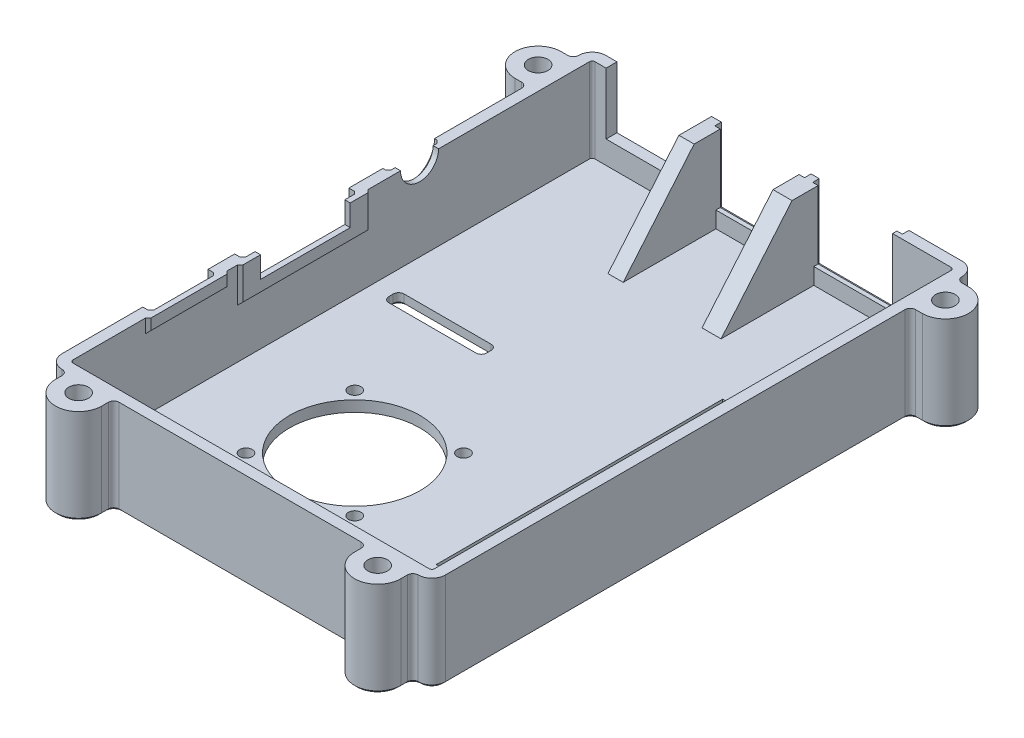
SolidWorks part; units mm, degrees
ref_plane "Front Plane" through (0, 0, 0) normal (0, 0, 1) x (1, 0, 0)
ref_plane "Top Plane" through (0, 0, 0) normal (0, 1, 0) x (1, 0, 0)
ref_plane "Right Plane" through (0, 0, 0) normal (1, 0, 0) x (0, 0, -1)
sketch "Sketch2" plane through (0, 0, 0) normal (0, 1, 0) x (1, 0, 0)
  line L1 (2.5, 0) -> (68, 0)
  line L2 (0, 2.5) -> (0, 97.5)
  line L3 (2.5, 100) -> (68, 100)
  line L4 (70.5, 2.5) -> (70.5, 97.5)
  arc A0 (0, 2.5) -> (2.5, 0) centre (2.5, 2.5) ccw
  arc A1 (68, 0) -> (70.5, 2.5) centre (68, 2.5) ccw
  arc A2 (70.5, 97.5) -> (68, 100) centre (68, 97.5) ccw
  arc A3 (2.5, 100) -> (0, 97.5) centre (2.5, 97.5) ccw
  point P7 (0, 0)
  point P10 (70.5, 0)
  point P13 (70.5, 100)
  point P16 (0, 100)
  dimension "D3" = 2.5
  dimension "D1" = 70.5
  dimension "D2" = 100
extrude "Base" add sketch "Sketch2" along normal blind 17.5
shell "Shell" thickness 2 removed face at (35.25, 17.5, -50)
sketch "Sketch14" plane through (0, 0, 0) normal (0, -1, 0) x (1, 0, 0)
  line L0 (35.25, 0) -> (35.25, -100) construction
  line L2 (68, -100) -> (2.5, -100) construction
  line L3 (-2.2, -88) -> (0, -88)
  line L4 (0, -97.5) -> (0, -2.5) construction
  line L5 (0, -88) -> (0, -96.5)
  line L6 (0, -96.5) -> (-2.2, -96.5)
  line L7 (3.5, 2.2) -> (3.5, 0)
  line L8 (2.5, 0) -> (68, 0) construction
  line L9 (3.5, 0) -> (12, 0)
  line L10 (12, 0) -> (12, 2.2)
  line L11 (72.7, -88) -> (70.5, -88)
  line L12 (70.5, -96.5) -> (72.7, -96.5)
  line L13 (70.5, -88) -> (70.5, -96.5)
  line L14 (58.5, 0) -> (58.5, 2.2)
  line L15 (67, 0) -> (58.5, 0)
  line L16 (67, 2.2) -> (67, 0)
  line L17 (2.5, 0) -> (68, 0) construction
  arc A0 (-2.2, -88) -> (-2.2, -96.5) centre (-2.2, -92.25) ccw
  arc A1 (3.5, 2.2) -> (12, 2.2) centre (7.75, 2.2) cw
  arc A2 (72.7, -88) -> (72.7, -96.5) centre (72.7, -92.25) cw
  arc A3 (67, 2.2) -> (58.5, 2.2) centre (62.75, 2.2) ccw
  dimension "D1" = 2.2
  dimension "D2" = 8.5
  dimension "D3" = 3.5
  dimension "D4" = 3.5
extrude "Clamps" add sketch "Sketch14" against normal up to surface (17.5 mm away) up to face at (35.25, 17.5, -50)
fillet "Clamp Fillets" radius 1 8 edges at (58.5, 8.75, 0) (67, 8.75, 0) (12, 8.75, 0) (3.5, 8.75, 0) (0, 8.75, -96.5) (0, 8.75, -88) (70.5, 8.75, -88) (70.5, 8.75, -96.5)
sketch "Sketch20" plane through (0, 0, 0) normal (0, -1, 0) x (1, 0, 0)
  circle A0 centre (7.75, 2.2) radius 1.8
  circle A1 centre (62.75, 2.2) radius 1.8
  circle A2 centre (72.7, -92.25) radius 1.8
  circle A3 centre (-2.2, -92.25) radius 1.8
  arc A4 (12, 2.2) -> (3.5, 2.2) centre (7.75, 2.2) ccw construction
  arc A5 (67, 2.2) -> (58.5, 2.2) centre (62.75, 2.2) ccw construction
  arc A6 (-2.2, -88) -> (-2.2, -96.5) centre (-2.2, -92.25) ccw construction
  arc A7 (72.7, -96.5) -> (72.7, -88) centre (72.7, -92.25) ccw construction
  dimension "D1" = 3.6
extrude "Clamp Holes" cut sketch "Sketch20" against normal through all
sketch "Sketch21" plane through (0, 0, 0) normal (0, -1, 0) x (1, 0, 0)
  circle A0 centre (7.75, 2.2) radius 2.9
  circle A1 centre (62.75, 2.2) radius 2.9
  circle A2 centre (72.7, -92.25) radius 2.9
  circle A3 centre (-2.2, -92.25) radius 2.9
  circle A4 centre (-2.2, -92.25) radius 1.8 construction
  circle A5 centre (7.75, 2.2) radius 1.8 construction
  circle A6 centre (62.75, 2.2) radius 1.8 construction
  circle A7 centre (72.7, -92.25) radius 1.8 construction
  dimension "D1" = 5.8
extrude "Clamp Countersinks" cut sketch "Sketch21" against normal blind 3.4
chamfer "Clamp Countersink Chamfers" distance 0.3 angle 45 4 edges at (-2.2, 0, -95.15) (72.7, 0, -95.15) (62.75, 0, -0.7) (7.75, 0, -0.7)
sketch "Sketch24" plane through (0, 0, -100) normal (0, 0, -1) x (-1, 0, 0)
  line L0 (-68, 17.5) -> (-2.5, 17.5) construction
  line L1 (-57.25, 17.5) -> (-42.75, 17.5)
  line L2 (-57.25, 17.5) -> (-57.25, 5)
  line L3 (-57.25, 5) -> (-42.75, 5)
  line L4 (-42.75, 17.5) -> (-42.75, 5)
  line L6 (0, 17.5) -> (0, 0) construction
  line L7 (-39.25, 17.5) -> (-24.75, 17.5)
  line L8 (-39.25, 17.5) -> (-39.25, 5)
  line L9 (-39.25, 5) -> (-24.75, 5)
  line L10 (-24.75, 17.5) -> (-24.75, 5)
  dimension "D1" = 14.5
  dimension "D2" = 24.75
  dimension "D3" = 42.75
  dimension "D4" = 12.5
extrude "USB Cutout" cut sketch "Sketch24" against normal blind 18.25
sketch "Sketch25" plane through (0, 0, -100) normal (0, 0, -1) x (-1, 0, 0)
  line L0 (-42.75, 17.5) -> (-39.25, 17.5) construction
  line L1 (-41.75, 17.5) -> (-58.25, 17.5)
  line L2 (-41.75, 17.5) -> (-41.75, 4)
  line L3 (-41.75, 4) -> (-58.25, 4)
  line L4 (-58.25, 17.5) -> (-58.25, 4)
  line L6 (-24.75, 17.5) -> (-2.5, 17.5) construction
  line L7 (-23.75, 17.5) -> (-40.25, 17.5)
  line L8 (-23.75, 17.5) -> (-23.75, 4)
  line L9 (-23.75, 4) -> (-40.25, 4)
  line L10 (-40.25, 17.5) -> (-40.25, 4)
  line L12 (-57.25, 17.5) -> (-57.25, 5) construction
  line L13 (-42.75, 5) -> (-42.75, 17.5) construction
  line L14 (-39.25, 17.5) -> (-39.25, 5) construction
  line L15 (-24.75, 5) -> (-24.75, 17.5) construction
  point P18 (-57.25, 11.25)
  dimension "D1" = 1
  dimension "D2" = 1
  dimension "D3" = 1
  dimension "D4" = 1
  dimension "D5" = 13.5
extrude "USB Approach" cut sketch "Sketch25" against normal blind 1.2
sketch "Sketch26" plane through (42.75, 0, 0) normal (1, 0, 0) x (0, 0, -1)
  line L0 (98, 2) -> (98, 17.5)
  line L1 (98, 17.5) -> (94, 17.5)
  line L2 (98, 2) -> (80.95, 2)
  line L3 (80.95, 2) -> (94, 17.5)
  line L4 (100, 4) -> (100, 17.5) construction
  line L5 (100, 4) -> (100, 17.5) construction
  dimension "D1" = 6
  dimension "D2" = 19.05
extrude "USB Inner Support" add sketch "Sketch26" against normal up to surface (3.5 mm away) up to face at (39.25, 11.25, -98.4)
sketch "Sketch27" plane through (24.75, 0, 0) normal (1, 0, 0) x (0, 0, -1)
  line L0 (98, 2) -> (98, 17.5)
  line L1 (98, 17.5) -> (94, 17.5)
  line L2 (98, 2) -> (80.95, 2)
  line L3 (80.95, 2) -> (94, 17.5)
  line L4 (100, 4) -> (100, 17.5) construction
  line L5 (100, 4) -> (100, 17.5) construction
  dimension "D1" = 6
  dimension "D2" = 19.05
extrude "USB Outer Support" add sketch "Sketch27" against normal blind 2.8
sketch "Sketch28" plane through (0, 0, -100) normal (0, 0, -1) x (-1, 0, 0)
  line L0 (-23.75, 17.5) -> (-2.5, 17.5) construction
  line L1 (-21.95, 17.5) -> (-4.55, 17.5)
  line L2 (-21.95, 17.5) -> (-21.95, 6.2)
  line L3 (-21.95, 6.2) -> (-4.55, 6.2)
  line L4 (-4.55, 17.5) -> (-4.55, 6.2)
  line L5 (0, 17.5) -> (0, 0) construction
  dimension "D1" = 17.4
  dimension "D2" = 4.55
  dimension "D3" = 11.3
extrude "RJ45 Cutout" cut sketch "Sketch28" against normal blind 22.7
sketch "Sketch29" plane through (2, 0, 0) normal (1, 0, 0) x (0, 0, -1)
  line L0 (97.5, 17.5) -> (2.5, 17.5) construction
  line L1 (15.85, 17.5) -> (30.85, 17.5)
  line L2 (15.85, 17.5) -> (15.85, 15)
  line L3 (15.85, 15) -> (30.85, 15)
  line L4 (30.85, 17.5) -> (30.85, 15)
  line L5 (0, 17.5) -> (0, 0) construction
  line L6 (32.75, 17.5) -> (56.75, 17.5)
  line L7 (32.75, 17.5) -> (32.75, 11.07)
  line L8 (32.75, 11.07) -> (56.75, 11.07)
  line L9 (56.75, 17.5) -> (56.75, 11.07)
  dimension "D1" = 24
  dimension "D2" = 15
  dimension "D3" = 15.85
  dimension "D4" = 32.75
  dimension "D5" = 2.5
  dimension "D6" = 6.43
extrude "HDMI Support" add sketch "Sketch29" along normal blind 0.5
chamfer "HDMI Support Chamfer" distance 0.5 angle 45 6 edges at (2.5, 14.285, -56.75) (2.5, 11.07, -44.75) (2.5, 14.285, -32.75) (2.5, 16.25, -30.85) (2.5, 15, -23.35) (2.5, 16.25, -15.85)
sketch "Sketch30" plane through (0, 0, 0) normal (-1, 0, 0) x (0, 0, 1)
  line L0 (-87, 17.5) -> (-2.5, 17.5) construction
  line L1 (-34.25, 17.5) -> (-55.25, 17.5)
  line L2 (-34.25, 17.5) -> (-34.25, 11.57)
  line L3 (-34.25, 11.57) -> (-55.25, 11.57)
  line L4 (-55.25, 17.5) -> (-55.25, 11.57)
  line L5 (0, 17.5) -> (0, 0) construction
  line L6 (-29.35, 17.5) -> (-17.35, 17.5)
  line L7 (-29.35, 17.5) -> (-29.35, 15.5)
  line L8 (-29.35, 15.5) -> (-17.35, 15.5)
  line L9 (-17.35, 17.5) -> (-17.35, 15.5)
  dimension "D1" = 12
  dimension "D2" = 21
  dimension "D3" = 17.35
  dimension "D4" = 34.25
  dimension "D5" = 5.93
  dimension "D6" = 2
extrude "HDMI Approach" cut sketch "Sketch30" against normal blind 1.5
sketch "Sketch31" plane through (1.5, 0, 0) normal (-1, 0, 0) x (0, 0, 1)
  line L0 (-34.25, 17.5) -> (-55.25, 17.5) construction
  line L1 (-53, 17.5) -> (-36.5, 17.5)
  line L2 (-53, 17.5) -> (-53, 13.57)
  line L3 (-53, 13.57) -> (-36.5, 13.57)
  line L4 (-36.5, 17.5) -> (-36.5, 13.57)
  line L5 (-55.25, 17.5) -> (-55.25, 11.57) construction
  line L6 (-34.25, 11.57) -> (-34.25, 17.5) construction
  line L7 (-55.25, 11.57) -> (-34.25, 11.57) construction
  dimension "D1" = 2.25
  dimension "D2" = 2.25
  dimension "D3" = 2
extrude "HDMI Cutout" cut sketch "Sketch31" against normal blind 1
chamfer "HDMI Approach Chamfer" distance 0.5 angle 45 6 edges at (1.5, 16.5, -17.35) (1.5, 15.5, -23.35) (1.5, 16.5, -29.35) (1.5, 14.535, -34.25) (1.5, 11.57, -44.75) (1.5, 14.535, -55.25)
sketch "Sketch32" plane through (0, 0, 0) normal (-1, 0, 0) x (0, 0, 1)
  line L0 (-87, 17.5) -> (-55.25, 17.5) construction
  line L1 (0, 17.5) -> (0, 0) construction
  circle A0 centre (-66.25, 17.5) radius 3.5
  dimension "D1" = 7
  dimension "D2" = 66.25
extrude "Audio Cutout" cut sketch "Sketch32" against normal blind 2
sketch "Sketch33" plane through (0, 0, 0) normal (-1, 0, 0) x (0, 0, 1)
  circle A0 centre (-66.25, 17.5) radius 4.75
  arc A1 (-69.75, 17.5) -> (-62.75, 17.5) centre (-66.25, 17.5) ccw construction
  dimension "D1" = 9.5
extrude "Audio Approach" cut sketch "Sketch33" against normal blind 1
chamfer "Audio Approach Chamfer" distance 0.5 angle 45 1 edges at (1, 12.75, -66.25)
sketch "Sketch34" plane through (0, 0, 0) normal (0, -1, 0) x (1, 0, 0)
  line L0 (70.5, -2.5) -> (70.5, -87) construction
  line L1 (52.5, -18.8) -> (58.5, -18.8)
  line L2 (52.5, -18.8) -> (52.5, -71.5)
  line L3 (52.5, -71.5) -> (58.5, -71.5)
  line L4 (58.5, -18.8) -> (58.5, -71.5)
  line L5 (13, 0) -> (57.5, 0) construction
  point P6 (55.5, -18.8)
  dimension "D1" = 6
  dimension "D2" = 52.7
  dimension "D3" = 12
  dimension "D4" = 18.8
extrude "Header Cutout" cut sketch "Sketch34" against normal blind 2
sketch "Sketch35" plane through (0, 0, 0) normal (0, -1, 0) x (1, 0, 0)
  line L0 (55.5, -18.8) -> (55.5, -71.5) construction
  line L1 (58.5, -18.8) -> (52.5, -18.8) construction
  line L2 (52.5, -71.5) -> (58.5, -71.5) construction
  line L3 (52.5, -45.15) -> (58.5, -45.15) construction
  line L4 (52.5, -18.8) -> (52.5, -71.5) construction
  line L5 (58.5, -71.5) -> (58.5, -18.8) construction
  line L6 (56, -18.8) -> (55, -18.8)
  line L7 (55, -18.8) -> (55, -19.8)
  line L8 (55, -19.8) -> (53.5, -19.8)
  line L9 (53.5, -19.8) -> (53.5, -24.7625)
  line L10 (53.5, -24.7625) -> (52.5, -24.7625)
  line L11 (52.5, -24.7625) -> (52.5, -25.7625)
  line L12 (52.5, -25.7625) -> (53.5, -25.7625)
  line L13 (53.5, -25.7625) -> (53.5, -37.6875)
  line L14 (53.5, -37.6875) -> (52.5, -37.6875)
  line L15 (52.5, -37.6875) -> (52.5, -38.6875)
  line L16 (52.5, -38.6875) -> (53.5, -38.6875)
  line L17 (53.5, -38.6875) -> (53.5, -43.65)
  line L18 (53.5, -43.65) -> (55, -43.65)
  line L19 (55, -43.65) -> (55, -44.65)
  line L20 (55, -44.65) -> (52.5, -44.65)
  line L21 (52.5, -44.65) -> (52.5, -45.65)
  line L22 (56, -71.5) -> (55, -71.5)
  line L23 (55, -45.65) -> (52.5, -45.65)
  line L24 (55, -46.65) -> (55, -45.65)
  line L25 (53.5, -46.65) -> (55, -46.65)
  line L26 (53.5, -51.6125) -> (53.5, -46.65)
  line L27 (52.5, -51.6125) -> (53.5, -51.6125)
  line L28 (52.5, -52.6125) -> (52.5, -51.6125)
  line L29 (53.5, -52.6125) -> (52.5, -52.6125)
  line L30 (53.5, -64.5375) -> (53.5, -52.6125)
  line L31 (52.5, -64.5375) -> (53.5, -64.5375)
  line L32 (52.5, -65.5375) -> (52.5, -64.5375)
  line L33 (53.5, -65.5375) -> (52.5, -65.5375)
  line L34 (53.5, -70.5) -> (53.5, -65.5375)
  line L35 (55, -70.5) -> (53.5, -70.5)
  line L36 (55, -71.5) -> (55, -70.5)
  line L37 (56, -71.5) -> (56, -70.5)
  line L38 (56, -70.5) -> (57.5, -70.5)
  line L39 (57.5, -70.5) -> (57.5, -65.5375)
  line L40 (57.5, -65.5375) -> (58.5, -65.5375)
  line L41 (58.5, -65.5375) -> (58.5, -64.5375)
  line L42 (58.5, -64.5375) -> (57.5, -64.5375)
  line L43 (57.5, -64.5375) -> (57.5, -52.6125)
  line L44 (57.5, -52.6125) -> (58.5, -52.6125)
  line L45 (58.5, -52.6125) -> (58.5, -51.6125)
  line L46 (58.5, -51.6125) -> (57.5, -51.6125)
  line L47 (57.5, -51.6125) -> (57.5, -46.65)
  line L48 (57.5, -46.65) -> (56, -46.65)
  line L49 (56, -46.65) -> (56, -45.65)
  line L50 (56, -45.65) -> (58.5, -45.65)
  line L51 (58.5, -44.65) -> (58.5, -45.65)
  line L52 (56, -44.65) -> (58.5, -44.65)
  line L53 (56, -43.65) -> (56, -44.65)
  line L54 (57.5, -43.65) -> (56, -43.65)
  line L55 (57.5, -38.6875) -> (57.5, -43.65)
  line L56 (58.5, -38.6875) -> (57.5, -38.6875)
  line L57 (58.5, -37.6875) -> (58.5, -38.6875)
  line L58 (57.5, -37.6875) -> (58.5, -37.6875)
  line L59 (57.5, -25.7625) -> (57.5, -37.6875)
  line L60 (58.5, -25.7625) -> (57.5, -25.7625)
  line L61 (58.5, -24.7625) -> (58.5, -25.7625)
  line L62 (57.5, -24.7625) -> (58.5, -24.7625)
  line L63 (57.5, -19.8) -> (57.5, -24.7625)
  line L64 (56, -19.8) -> (57.5, -19.8)
  line L65 (56, -18.8) -> (56, -19.8)
  dimension "D1" = 0.5
  dimension "D2" = 1
  dimension "D3" = 1.5
  dimension "D4" = 11.925
extrude "Header Cover" add sketch "Sketch35" against normal blind 1
chamfer "Shell Chamfer" distance 0.5 angle 45 44 edges at (53.75, 0, -71.5) (52.5, 0, -68.5187) (52.5, 0, -58.575) (52.5, 0, -48.6313) (52.5, 0, -41.6688) (52.5, 0, -31.725) (52.5, 0, -21.7813) (53.75, 0, -18.8) (57.25, 0, -18.8) (58.5, 0, -21.7813) (58.5, 0, -31.725) (58.5, 0, -41.6688) (58.5, 0, -48.6313) (58.5, 0, -58.575) (58.5, 0, -68.5187) (57.25, 0, -71.5) (69.7678, 0, -99.2678) (70.7929, 0, -96.7929) (72.1, 0, -96.5) (76.95, 0, -92.25) (72.1, 0, -88) (70.7929, 0, -87.7071) (70.5, 0, -44.75) (35.25, 0, -100) (0.7322, 0, -99.2678) (-0.2929, 0, -96.7929) (-1.6, 0, -96.5) (-6.45, 0, -92.25) (-1.6, 0, -88) (0, 0, -44.75) (69.7678, 0, -0.7322) (67.2929, 0, 0.2929) (67, 0, 1.6) (62.75, 0, 6.45) (58.5, 0, 1.6) (58.2071, 0, 0.2929) (0.7322, 0, -0.7322) (3.5, 0, 1.6) (7.75, 0, 6.45) (12, 0, 1.6) (12.2929, 0, 0.2929) (35.25, 0, 0) (-0.2929, 0, -87.7071) (3.2071, 0, 0.2929)
sketch "Sketch38" plane through (0, 0, 0) normal (0, -1, 0) x (1, 0, 0)
  line L0 (68, -100) -> (2.5, -100) construction
  line L1 (6.45, -56.157) -> (22.45, -56.157)
  line L2 (5.45, -57.157) -> (5.45, -57.957)
  line L3 (6.45, -58.957) -> (22.45, -58.957)
  line L4 (23.45, -57.157) -> (23.45, -57.957)
  line L5 (0, -87) -> (0, -2.5) construction
  arc A0 (22.45, -56.157) -> (23.45, -57.157) centre (22.45, -57.157) cw
  arc A1 (23.45, -57.957) -> (22.45, -58.957) centre (22.45, -57.957) cw
  arc A2 (6.45, -58.957) -> (5.45, -57.957) centre (6.45, -57.957) cw
  arc A3 (5.45, -57.157) -> (6.45, -56.157) centre (6.45, -57.157) cw
  point P12 (23.45, -58.957)
  point P15 (5.45, -58.957)
  point P18 (5.45, -56.157)
  dimension "D5" = 1
  dimension "D1" = 18
  dimension "D2" = 2.8
  dimension "D3" = 41.043
  dimension "D4" = 5.45
extrude "Ribbon Slot" cut sketch "Sketch38" against normal up to surface (2 mm away) up to face at (55.5, 2, -45.15)
chamfer "Ribbon Slot Chamfer" distance 0.5 angle 45 8 edges at (14.45, 0, -56.157) (23.1571, 0, -56.4499) (23.45, 0, -57.557) (23.1571, 0, -58.6641) (14.45, 0, -58.957) (5.7429, 0, -58.6641) (5.45, 0, -57.557) (5.7429, 0, -56.4499)
sketch "Sketch39" plane through (0, 0, 0) normal (0, -1, 0) x (1, 0, 0)
  line L0 (0, -87) -> (0, -2.5) construction
  line L1 (13, 0) -> (57.5, 0) construction
  line L2 (27.25, -29.0785) -> (41.3921, -29.0785) construction
  line L3 (27.25, -14.9364) -> (27.25, -41.0785) construction
  line L4 (27.25, -29.0785) -> (37.25, -19.0785) construction
  circle A0 centre (27.25, -29.0785) radius 14.1421 construction
  circle A1 centre (27.25, -29.0785) radius 12
  circle A2 centre (37.25, -19.0785) radius 1.15
  circle A3 centre (37.25, -39.0785) radius 1.15
  circle A4 centre (17.25, -39.0785) radius 1.15
  circle A5 centre (17.25, -19.0785) radius 1.15
  dimension "D3" = 28.2842
  dimension "D4" = 24
  dimension "D6" = 2.3
  dimension "D1" = 27.25
  dimension "D2" = 29.0785
  dimension "D5" = 45
extrude "Fan Mount" cut sketch "Sketch39" against normal up to surface (2 mm away) up to face at (14.45, 2, -57.557)
